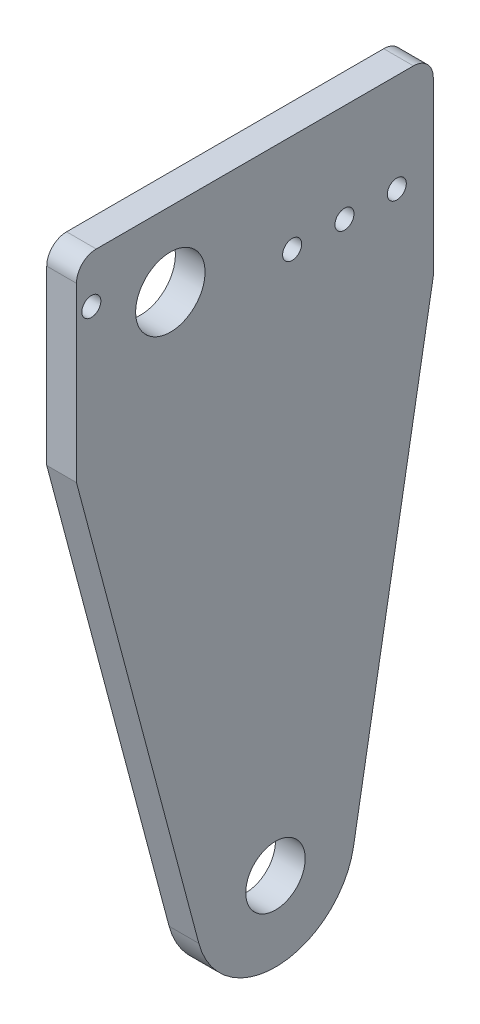
SolidWorks part; units mm, degrees
ref_plane "Front Plane" through (0, 0, 0) normal (0, 0, 1) x (1, 0, 0)
ref_plane "Top Plane" through (0, 0, 0) normal (0, 1, 0) x (1, 0, 0)
ref_plane "Right Plane" through (0, 0, 0) normal (1, 0, 0) x (0, 0, -1)
sketch "Sketch1" plane through (0, 0, 0) normal (1, 0, 0) x (0, 0, -1)
  line L0 (42.1132, 8.7376) -> (42.1132, -18.8943)
  line L1 (-15.0368, 8.7376) -> (-15.0368, -18.8943)
  line L2 (38.9382, 11.9126) -> (-11.8618, 11.9126)
  line L3 (-15.7317, -3.8354) -> (28.7183, -3.8354) construction
  line L4 (-15.0368, -18.8943) -> (4.564, -92.6295)
  line L5 (42.1132, -18.8943) -> (29.3462, -91.5644)
  line L9 (-9.4805, 9.4615) -> (-9.4805, 0) construction
  line L10 (-12.8841, 9.4615) -> (-9.4805, 9.4615) construction
  circle A0 centre (16.8378, -89.3668) radius 4.7625
  arc A1 (4.564, -92.6295) -> (29.3462, -91.5644) centre (16.8378, -89.3668) ccw
  circle A2 centre (0, 0) radius 5.5626
  circle A3 centre (-12.6555, 4.3307) radius 1.524
  arc A4 (42.1132, 8.7376) -> (38.9382, 11.9126) centre (38.9382, 8.7376) ccw
  circle A5 centre (16.8378, -89.3668) radius 77.47 construction
  circle A6 centre (36.2712, -3.8354) radius 1.524
  circle A7 centre (27.8892, -3.8354) radius 1.524
  circle A8 centre (19.5072, -3.8354) radius 1.524
  circle A9 centre (11.1252, -3.8354) radius 1.524 [skipped]
  arc A10 (-15.0368, 8.7376) -> (-11.8618, 11.9126) centre (-11.8618, 8.7376) cw
  dimension "D1" = 3.175
  dimension "D2" = 12.7
  dimension "D3" = 154.94
  dimension "D4" = 11.1252
  dimension "D6" = 3.048
  dimension "D9" = 3.048
  dimension "D13" = 5.1308
  dimension "D15" = 9.525
  dimension "D5" = 11.9126
  dimension "D8" = 5.842
  dimension "D10" = 2.3813
  dimension "D11" = 15.748
  dimension "D12" = 5.5562
  dimension "D14" = 57.15
  dimension "D7" = 3
extrude "Boss-Extrude1" add sketch "Sketch1" along normal blind 4.7625
